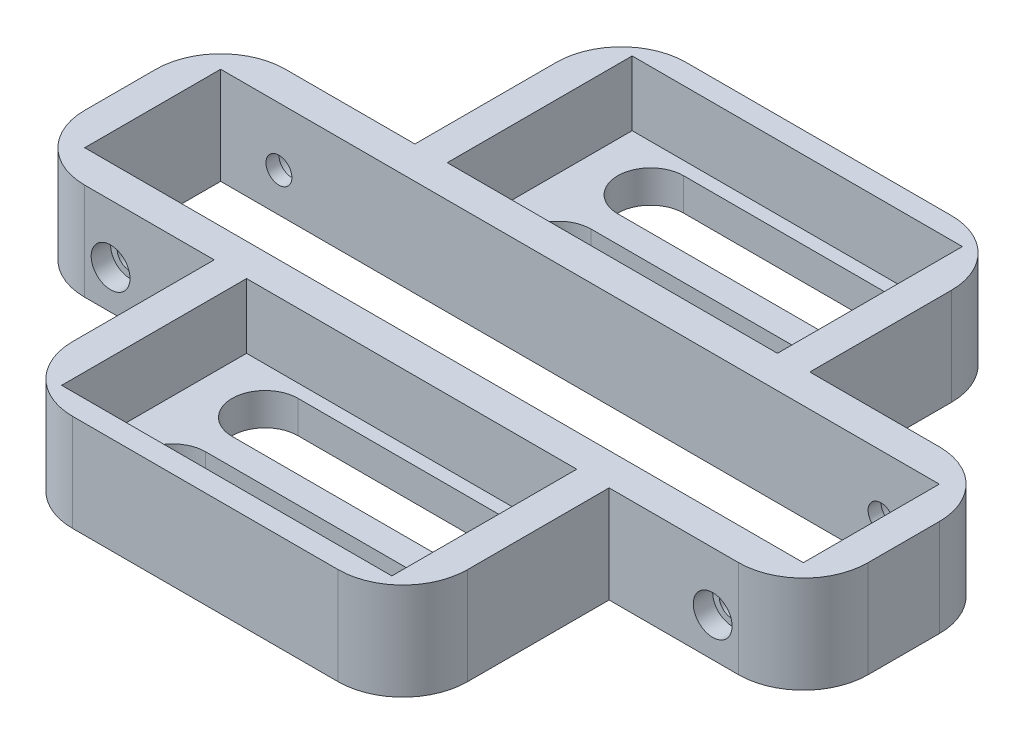
SolidWorks part; units mm, degrees
other "Markup1"
sketch "Sketch4" plane through (-60.5, 10, 46.36) normal (-0.2171, 0.8708, 0.4411) x (0.5241, -0.2773, 0.8053)
ref_plane "Front Plane" through (0, 0, 0) normal (0, 0, 1) x (1, 0, 0)
ref_plane "Top Plane" through (0, 0, 0) normal (0, 1, 0) x (1, 0, 0)
ref_plane "Right Plane" through (0, 0, 0) normal (1, 0, 0) x (0, 0, -1)
sketch "Sketch1" plane through (0, 0, 0) normal (0, 1, 0) x (1, 0, 0)
  line L0 (0, 47.36) -> (0, -47.36) construction
  line L1 (-30.5, -47.36) -> (30.5, -47.36)
  line L2 (-30.5, -47.36) -> (-30.5, -15.5)
  line L3 (-30.5, 47.36) -> (30.5, 47.36)
  line L4 (30.5, -47.36) -> (30.5, -15.5)
  line L5 (-30.5, -47.36) -> (30.5, 47.36) construction
  line L6 (-30.5, 47.36) -> (30.5, -47.36) construction
  line L11 (-30.5, -15.5) -> (30.5, 15.5) construction
  line L12 (-30.5, 15.5) -> (30.5, -15.5) construction
  line L13 (30.5, 15.5) -> (60.5, 15.5)
  line L15 (30.5, -15.5) -> (60.5, -15.5)
  line L16 (60.5, 15.5) -> (60.5, -15.5)
  line L22 (30.5, 15.5) -> (-30.5, 15.5)
  line L23 (-30.5, -15.5) -> (30.5, -15.5)
  line L24 (-30.5, -15.5) -> (-60.5, -15.5)
  line L25 (-60.5, 15.5) -> (-60.5, -15.5)
  line L26 (-30.5, 15.5) -> (-60.5, 15.5)
  line L28 (-30.5, 15.5) -> (-30.5, 47.36)
  line L29 (30.5, 15.5) -> (30.5, 47.36)
  line L30 (-30.5, 10.5) -> (-55.5, 10.5)
  line L31 (-55.5, 10.5) -> (-55.5, -10.5)
  line L32 (-30.5, -10.5) -> (-55.5, -10.5)
  line L33 (-30.5, -10.5) -> (30.5, -10.5)
  line L34 (30.5, -10.5) -> (55.5, -10.5)
  line L35 (55.5, 10.5) -> (55.5, -10.5)
  line L36 (30.5, 10.5) -> (55.5, 10.5)
  line L37 (30.5, 10.5) -> (-30.5, 10.5)
  line L38 (-60.5, 0) -> (60.5, 0) construction
  line L39 (-25.5, 44.06) -> (25.5, 44.06)
  line L40 (-25.5, 44.06) -> (-25.5, 15.5)
  line L41 (-25.5, 15.5) -> (25.5, 15.5)
  line L42 (25.5, 44.06) -> (25.5, 15.5)
  line L43 (-25.5, -15.5) -> (25.5, -15.5)
  line L44 (25.5, -44.06) -> (25.5, -15.5)
  line L45 (-25.5, -44.06) -> (25.5, -44.06)
  line L46 (-25.5, -44.06) -> (-25.5, -15.5)
  line L47 (-15.5, 36.92) -> (15.5, 36.92) construction
  line L48 (-15.5, 42.01) -> (15.5, 42.01)
  line L49 (-15.5, 31.83) -> (15.5, 31.83)
  line L50 (-25.5, 29.78) -> (25.5, 29.78) construction
  line L51 (-15.5, 22.64) -> (15.5, 22.64) construction
  line L52 (-15.5, 17.55) -> (15.5, 17.55)
  line L53 (-15.5, 27.73) -> (15.5, 27.73)
  line L54 (-15.5, -22.64) -> (15.5, -22.64) construction
  line L55 (-15.5, -17.55) -> (15.5, -17.55)
  line L56 (-15.5, -27.73) -> (15.5, -27.73)
  line L57 (-15.5, -36.92) -> (15.5, -36.92) construction
  line L58 (-15.5, -42.01) -> (15.5, -42.01)
  line L59 (-15.5, -31.83) -> (15.5, -31.83)
  arc A0 (-15.5, 42.01) -> (-15.5, 31.83) centre (-15.5, 36.92) ccw
  arc A1 (15.5, 31.83) -> (15.5, 42.01) centre (15.5, 36.92) ccw
  arc A2 (-15.5, 17.55) -> (-15.5, 27.73) centre (-15.5, 22.64) cw
  arc A3 (15.5, 27.73) -> (15.5, 17.55) centre (15.5, 22.64) cw
  arc A4 (-15.5, -17.55) -> (-15.5, -27.73) centre (-15.5, -22.64) ccw
  arc A5 (15.5, -27.73) -> (15.5, -17.55) centre (15.5, -22.64) ccw
  arc A6 (-15.5, -42.01) -> (-15.5, -31.83) centre (-15.5, -36.92) cw
  arc A7 (15.5, -31.83) -> (15.5, -42.01) centre (15.5, -36.92) cw
  point P0 (0, 0)
  point P5 (0, 0)
  point P29 (0, 44.06)
  point P38 (0, 36.92)
  point P50 (0, 22.64)
  point P57 (0, -22.64)
  point P64 (0, -36.92)
  dimension "D1" = 61
  dimension "D4" = 30
  dimension "D2" = 31.86
  dimension "D3" = 31
  dimension "D6" = 51
  dimension "D7" = 28.56
  dimension "D8" = 10.18
  dimension "D10" = 31
  dimension "D9" = 7.14
  dimension "D5" = 5
extrude "Boss-Extrude1" add sketch "Sketch1" along normal blind 10 contours L39 L42 L22 L29 L3 L28 L40 | L22 L26 L25 L24 L23 L15 L16 L13 L37 L36 L35 L34 L33 L32 L31 L30 | L45 L46 L23 L2 L1 L4 L44 region at (-29.8118, 0, 31.43) region at (-45.5, 0, 14.2509) region at (-29.8118, 0, -31.43)
extrude "Boss-Extrude2" add sketch "Sketch1<3>" against normal blind 5 contours L45 L46 L23 L2 L1 L4 L44 | L46 L45 L44 L23 | L22 L26 L25 L24 L23 L15 L16 L13 L37 L36 L35 L34 L33 L32 L31 L30 | L39 L42 L22 L29 L3 L28 L40 | L42 L39 L40 L22 region at (-29.8118, 0, 31.43) region at (-45.5, 0, 14.2509) region at (0, 0, 29.78) region at (-29.8118, 0, -31.43) region at (0, 0, -29.78)
sketch "Sketch1<3>" plane through (0, 0, 0) normal (0, 1, 0) x (1, 0, 0) same geometry as "Sketch1"
sketch "Sketch3" plane through (0, 0, 0) normal (0, 0, 1) x (1, 0, 0)
  line L0 (0, 10) -> (0, -5) construction
  line L1 (-60.5, 10) -> (-30.5, 10)
  line L2 (-60.5, 10) -> (-60.5, -5)
  line L3 (-60.5, -5) -> (-30.5, -5)
  line L4 (-30.5, 10) -> (-30.5, -5)
  line L5 (-30.5, 10) -> (30.5, 10) construction
  line L6 (0, -55) -> (0, 55) construction
  line L7 (-30.5, -5) -> (30.5, -5) construction
  circle A0 centre (-46.5, 1) radius 3
  circle A1 centre (-46.5, 1) radius 2
  circle A2 centre (46.5, 1) radius 2
  circle A3 centre (46.5, 1) radius 3
  dimension "D3" = 6
  dimension "D4" = 4
  dimension "D1" = 16
  dimension "D2" = 6
extrude "Cut-Extrude1" cut sketch "Sketch3" against normal up to surface and the other way up to surface contours A1 | A0 A1 | A2 | A3 A2 region at (-49.4151, 1, 0) region at (-46.5, 1, 0) region at (46.5, 1, 0) region at (43.5849, 1, 0) up to face at (-45.5, 2.5, -15.5) other way up to face at (-45.5, 2.5, 15.5)
extrude "Boss-Extrude3" add sketch "Sketch3<5>" along normal blind 12.5 and the other way blind 12.5 contours A0 A1 | A3 A2 region at (-49.4151, 1, 0) region at (43.5849, 1, 0)
sketch "Sketch3<5>" plane through (0, 0, 0) normal (0, 0, 1) x (1, 0, 0) same geometry as "Sketch3"
extrude "Cut-Extrude5" cut sketch "Sketch3<12>" against normal blind 10.5 and the other way up to surface (10.5 mm away) contours A3 A2 | A0 A1 region at (-49.4151, 1, 0) region at (43.5849, 1, 0) other way up to face at (43.5, 1, 10.5)
sketch "Sketch3<12>" plane through (0, 0, 0) normal (0, 0, 1) x (1, 0, 0) same geometry as "Sketch3"
fillet "Fillet1" radius 10 8 edges at (30.5, 2.5, -47.36) (60.5, 2.5, -15.5) (60.5, 2.5, 15.5) (30.5, 2.5, 47.36) (-30.5, 2.5, -47.36) (-60.5, 2.5, -15.5) (-30.5, 2.5, 47.36) (-60.5, 2.5, 15.5)
equation "\"W_d\"= 15mm"
equation "\"F\"= 17.5"
equation "\"A\"= 31mm"
equation "\"G\"= 18.15mm"
equation "\"W_t\"= 5mm"
equation "\"B\"= 51mm"
equation "\"E\"= 14.18mm"
equation "\"D1@Sketch1\"= \"B\" + 2 * \"W_t\""
equation "\"D4@Sketch1\"= \"W_d\" + 15"
equation "\"D2@Sketch1\" = \"E\" * 2 + 3.5mm"
equation "\"D3@Sketch1\"= \"A\""
equation "\"D6@Sketch1\"= \"B\""
equation "\"D7@Sketch1\" = 2 * \"E\" + 0.2mm"
equation "\"B_d1\"= 4mm"
equation "\"B_d2\"= 6mm"
equation "\"S1\"= 16mm"
equation "\"S2\"= 6mm"
equation "\"D2@Sketch3\"= \"S2\""
equation "\"D1@Sketch3\"= \"S1\""
equation "\"D4@Sketch3\"= \"B_d1\""
equation "\"D3@Sketch3\"= \"B_d2\""
equation "\"D8@Sketch1\"= \"E\" - 4mm"
equation "\"D10@Sketch1\" = \"B\" - 20mm"
equation "\"D9@Sketch1\"= ( 2 * \"E\" + 0.2 ) / 4"
